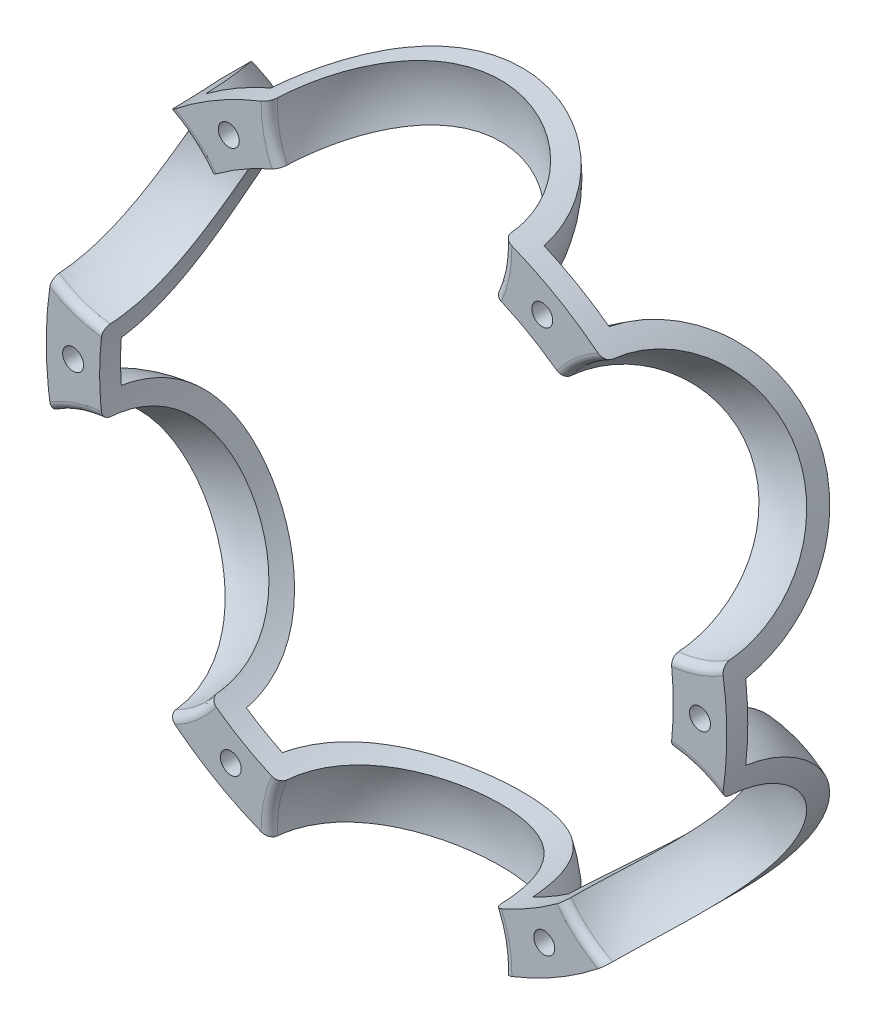
SolidWorks part; units mm, degrees
material "Dövülebilir Dökme Demir"
ref_plane "Ön Düzlem" through (0, 0, 0) normal (0, 0, 1) x (1, 0, 0)
ref_plane "Üst Düzlem" through (0, 0, 0) normal (0, 1, 0) x (1, 0, 0)
ref_plane "Sağ Düzlem" through (0, 0, 0) normal (1, 0, 0) x (0, 0, -1)
sketch "Çizim1" plane through (0, 0, 0) normal (0, 0, 1) x (1, 0, 0)
  circle A0 centre (0, 0) radius 6.85
  circle A1 centre (0, 0) radius 8.125
  dimension "D1" = 16.25
  dimension "D2" = 13.7
extrude "Yükseklik-Ekstrüzyon1" add sketch "Çizim1" along normal blind 4 from offset 0
sketch "Çizim2" plane through (0, 0, 4) normal (0, 0, 1) x (1, 0, 0)
  line L0 (0, 0) -> (0, 10.275) construction
  line L1 (0, 10.275) -> (0, 4.675)
  arc A0 (0, 4.675) -> (0, 10.275) centre (0, 7.475) ccw
  circle A2 centre (0, 0) radius 7.475 construction
  dimension "D2" = 2.8
revolve "Kes-Döndür1" cut sketch "Çizim2" angle 360 about L0
fillet "Radyus1" radius 0.2 1 edges at (-2.7553, 6.9767, 4)
fillet "Radyus2" radius 0.2 1 edges at (2.7553, 6.9767, 4)
pattern_circular "Dairesel Kaplama1" count 6 over 360 about axis through (0, 0, 0) along (0, 0, 1) of "Radyus1", "Kes-Döndür1", "Radyus2"
shell "İç Boşaltma3" thickness 0.5
sketch "Çizim5" plane through (0, 0, 0) normal (0, 0, 1) x (1, 0, 0)
  circle A0 centre (0, 0) radius 7.475 construction
sketch "Çizim6" plane through (0, 0, 4) normal (0, 0, 1) x (1, 0, 0)
  circle A0 centre (-3.7654, 6.4674) radius 0.25
  circle A1 centre (0, 0) radius 7.4837 construction
extrude "Kes-Ekstrüzyon1" cut sketch "Çizim6" against normal blind 3
pattern_circular "Dairesel Kaplama2" count 6 every 60 about axis through (0, 0, 0) along (0, 0, 1) of "Kes-Ekstrüzyon1"
